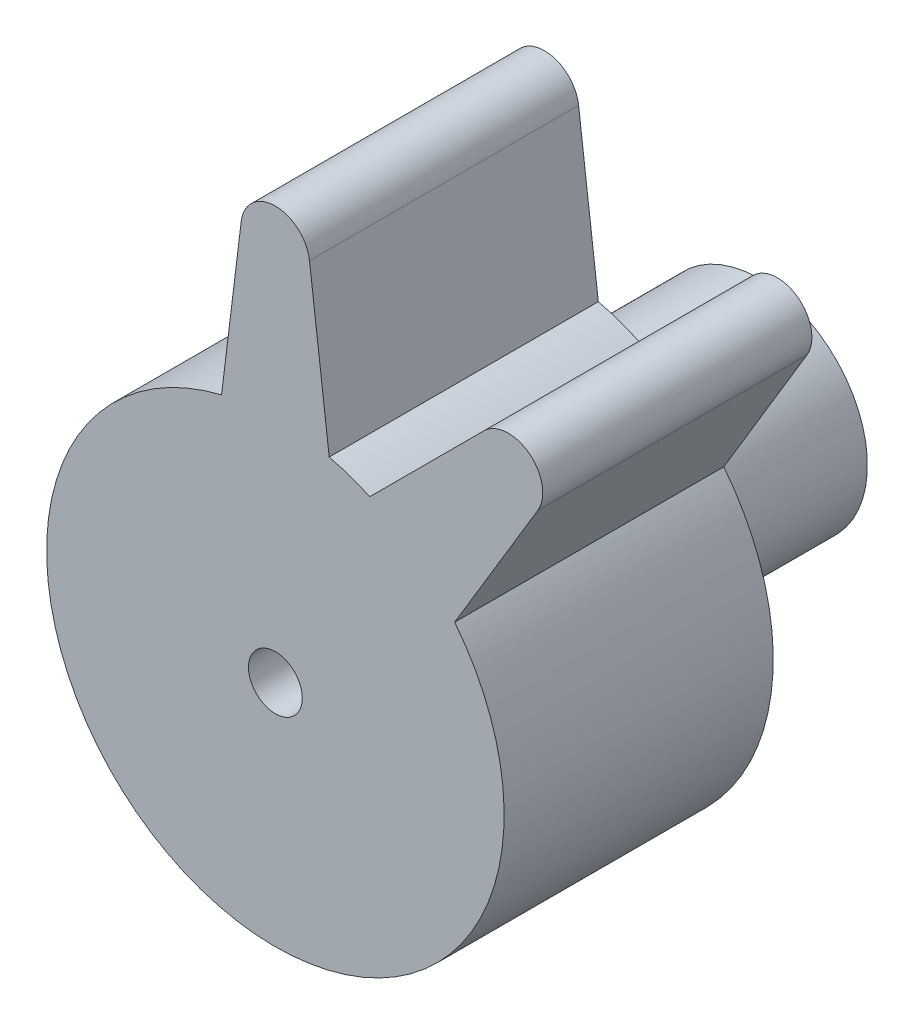
SolidWorks part; units mm, degrees
ref_plane "Front Plane" through (0, 0, 0) normal (0, 0, 1) x (1, 0, 0)
ref_plane "Top Plane" through (0, 0, 0) normal (0, 1, 0) x (1, 0, 0)
ref_plane "Right Plane" through (0, 0, 0) normal (1, 0, 0) x (0, 0, -1)
sketch "Sketch1" plane through (0, 0, 0) normal (0, 0, 1) x (1, 0, 0)
  line L0 (0, 0) -> (0, 51.188) construction
  line L1 (-2, 8.2614) -> (-1.2688, 14.2166)
  line L2 (2, 8.2614) -> (1.2688, 14.2166)
  line L3 (0, 0) -> (22.4184, 65.1077) construction
  line L4 (6.6622, 5.2787) -> (9.7524, 10.4217)
  line L5 (0, 0) -> (31.5145, 40.3367) construction
  line L6 (3.5102, 7.7414) -> (7.7528, 11.984)
  circle A0 centre (0, 0) radius 8.5
  circle A1 centre (0, 0) radius 1
  arc A2 (-1.2688, 14.2166) -> (1.2688, 14.2166) centre (0, 14.0608) cw
  arc A3 (9.7524, 10.4217) -> (7.7528, 11.984) centre (8.6567, 11.0801) ccw
  circle A4 centre (0, 0) radius 12 construction
  dimension "D1" = 24
  dimension "D2" = 17
  dimension "D3" = 2
  dimension "D4" = 7
  dimension "D7" = 6
  dimension "D5" = 4
  dimension "D6" = 19
extrude "Boss-Extrude1" add sketch "Sketch1" along normal blind 10 contours A0 A1 | A2 L1 A0 L2 | A0 region at (0, 11.4772, 0) region at (0, 8.2596, 0) region at (7.066, 9.0441, 0)
sketch "Sketch5" plane through (0, 0, 0) normal (0, 0, -1) x (-1, 0, 0)
  line L0 (1.3229, -1.5) -> (1.3229, 1.5)
  line L1 (3.7081, -1.5) -> (3.7081, 1.5)
  circle A0 centre (0, 0) radius 2
  circle A1 centre (0, 0) radius 4
  arc M7 (-2, 8.2614) -> (-3.5102, 7.7414) centre (0, 0) ccw
  dimension "D1" = 8
  dimension "D2" = 4
  dimension "D3" = 3
  dimension "D4" = 3
extrude "Boss-Extrude3" add sketch "Sketch5" along normal blind 8 contours L0 A0 | A1 A0 M7 region at (-1.5981, 0, 0) region at (3.8889, 0, 0)
